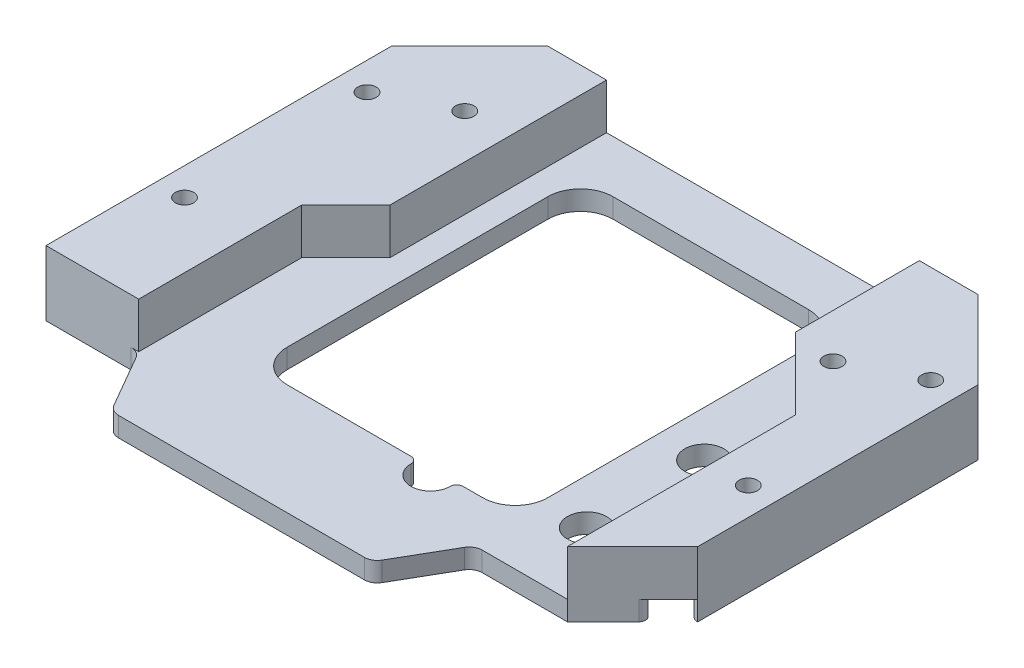
SolidWorks part; units mm, degrees
ref_plane "前视基准面" through (0, 0, 0) normal (0, 0, 1) x (1, 0, 0)
ref_plane "上视基准面" through (0, 0, 0) normal (0, 1, 0) x (1, 0, 0)
ref_plane "右视基准面" through (0, 0, 0) normal (1, 0, 0) x (0, 0, -1)
sketch "草图1" plane through (0, 0, 0) normal (0, 1, 0) x (1, 0, 0)
  line L0 (-40, 22) -> (-40, -31)
  line L1 (50, 22) -> (50, -21)
  line L2 (-35.75, 0) -> (35.75, 0) construction
  line L3 (-35.75, 14) -> (-35.75, -14) construction
  line L4 (-40, 22) -> (-28, 34)
  line L5 (-28, 34) -> (38, 34)
  line L6 (38, 34) -> (50, 22)
  line L7 (-25.75, 5) -> (45.75, 5) construction
  line L8 (45.75, 19) -> (45.75, -9) construction
  line L9 (-40, -31) -> (-25.7735, -31)
  line L10 (50, -21) -> (40, -31)
  line L11 (35.75, 0) -> (35.75, 14) construction
  line L12 (-25.7735, -31) -> (-20, -41)
  line L13 (-20, -41) -> (20, -41)
  line L14 (20, -41) -> (25.7735, -31)
  line L15 (25.7735, -31) -> (40, -31)
  line L16 (-15, 26) -> (25, 26)
  line L17 (-15, 26) -> (-15, -24)
  line L18 (-15, -24) -> (25, -24)
  line L19 (25, 26) -> (25, -24)
  line L20 (-25.75, 5) -> (-25.75, 19) construction
  circle A0 centre (-35.75, 14) radius 1.4
  circle A1 centre (35.75, 14) radius 1.4
  circle A2 centre (-35.75, -14) radius 1.4
  circle A3 centre (45.75, 19) radius 1.4
  circle A4 centre (45.75, -9) radius 1.4
  circle A5 centre (-25.75, 19) radius 1.4
  point P3 (50, -31)
  point P30 (0, -41)
  point P31 (5, 26)
  point P32 (5, 34)
  point P33 (0, 0)
  point P34 (0, 0)
  dimension "D5" = 2.8
  dimension "D8" = 10
  dimension "D1" = 40
  dimension "D2" = 50
  dimension "D3" = 28
  dimension "D4" = 71.5
  dimension "D6" = 20
  dimension "D7" = 45
  dimension "D9" = 5
  dimension "D10" = 12
  dimension "D11" = 12
  dimension "D12" = 65
  dimension "D16" = 60
  dimension "D15" = 10
  dimension "D13" = 40
  dimension "D17" = 60
  dimension "D18" = 8
  dimension "D19" = 40
  dimension "D20" = 50
extrude "凸台-拉伸1" add sketch "草图1" along normal blind 3
sketch "草图2" plane through (0, 3, 0) normal (0, 1, 0) x (1, 0, 0)
  line L0 (-19, 34) -> (-19, 0.7735)
  line L1 (38, 34) -> (-28, 34) construction
  line L3 (29, 34) -> (29, 15)
  line L5 (-19, 0.7735) -> (-25.7735, -6)
  line L6 (-25.7735, -6) -> (-25.7735, -31)
  line L7 (29, 15) -> (40, 4)
  line L8 (40, 4) -> (40, -31)
  line L9 (25.7735, -31) -> (40, -31) construction
  line L11 (-19, 34) -> (-28, 34)
  line L22 (-28, 34) -> (-40, 22)
  line L23 (-40, 22) -> (-40, -31)
  line L24 (-40, -31) -> (-25.7735, -31)
  line L25 (-25.7735, -31) -> (-20, -41)
  line L26 (-20, -41) -> (20, -41)
  line L27 (20, -41) -> (25.7735, -31)
  line L28 (25.7735, -31) -> (40, -31)
  line L29 (40, -31) -> (50, -21)
  line L30 (50, -21) -> (50, 22)
  line L31 (50, 22) -> (38, 34)
  line L32 (38, 34) -> (-28, 34)
  line L33 (-28, 34) -> (-40, 22)
  line L34 (-40, 22) -> (-40, -31)
  line L35 (-40, -31) -> (-25.7735, -31)
  line L40 (40, -31) -> (50, -21)
  line L41 (50, -21) -> (50, 22)
  line L42 (50, 22) -> (38, 34)
  line L43 (38, 34) -> (29, 34)
  circle A1 centre (45.75, -9) radius 1.4 construction
  circle A2 centre (45.75, 19) radius 1.4 construction
  circle A3 centre (-35.75, -14) radius 1.4 construction
  circle A4 centre (-35.75, 14) radius 1.4 construction
  circle A6 centre (35.75, 14) radius 1.4 construction
  circle A7 centre (45.75, -9) radius 1.4
  circle A8 centre (45.75, 19) radius 1.4
  circle A9 centre (-35.75, -14) radius 1.4
  circle A10 centre (-35.75, 14) radius 1.4
  circle A11 centre (-25.75, 19) radius 1.4 construction
  circle A12 centre (35.75, 14) radius 1.4
  circle A13 centre (-25.75, 19) radius 1.4
  point P1 (35.75, 14)
  dimension "D1" = 48
  dimension "D2" = 9
  dimension "D3" = 25
  dimension "D4" = 45
  dimension "D6" = 45
  dimension "D7" = 35
  dimension "D8" = 0
extrude "凸台-拉伸2" add sketch "草图2" along normal blind 7
sketch "草图3" plane through (0, 0, -34) normal (0, 0, -1) x (-1, 0, 0)
  line L0 (-38, 0) -> (28, 0) construction
  line L1 (-29, 3) -> (19, 3) construction
  circle A0 centre (-33, 6) radius 1.4
  circle A1 centre (23, 6) radius 1.4
  point P9 (-5, 3)
  dimension "D1" = 2.8
  dimension "D2" = 6
  dimension "D3" = 28
  dimension "D4" = 28
extrude "切除-拉伸1" cut sketch "草图3" against normal blind 7
sketch "草图4" plane through (0, 0, 0) normal (0, -1, 0) x (1, 0, 0)
  line L0 (38, -34) -> (-28, -34) construction
  line L1 (50, 21) -> (50, -22) construction
  line L2 (46, 21) -> (46, 1) construction
  line L3 (32, 20) -> (32, 2) construction
  circle A0 centre (46, 21) radius 3
  circle A1 centre (46, 1) radius 3
  circle A2 centre (32, 20) radius 3
  circle A3 centre (32, 2) radius 3
  circle A4 centre (13, 25) radius 3
  point P12 (32, 11)
  point P13 (46, 11)
  dimension "D1" = 35
  dimension "D2" = 20
  dimension "D3" = 4
  dimension "D4" = 6
  dimension "D8" = 37
  dimension "D5" = 18
  dimension "D6" = 18
  dimension "D7" = 59
extrude "切除-拉伸2" cut sketch "草图4" against normal blind 3
fillet "圆角1" radius 1 4 edges at (47.2929, 1.5, 23.7071) (48.7071, 1.5, 22.2929) (15.8284, 1.5, 24) (10.1716, 1.5, 24)
fillet "圆角2" radius 2 4 edges at (-25.7735, 1.5, 31) (-20, 1.5, 41) (20, 1.5, 41) (25.7735, 1.5, 31)
fillet "圆角3" radius 5 4 edges at (25, 1.5, -26) (25, 1.5, 24) (-15, 1.5, 24) (-15, 1.5, -26)
